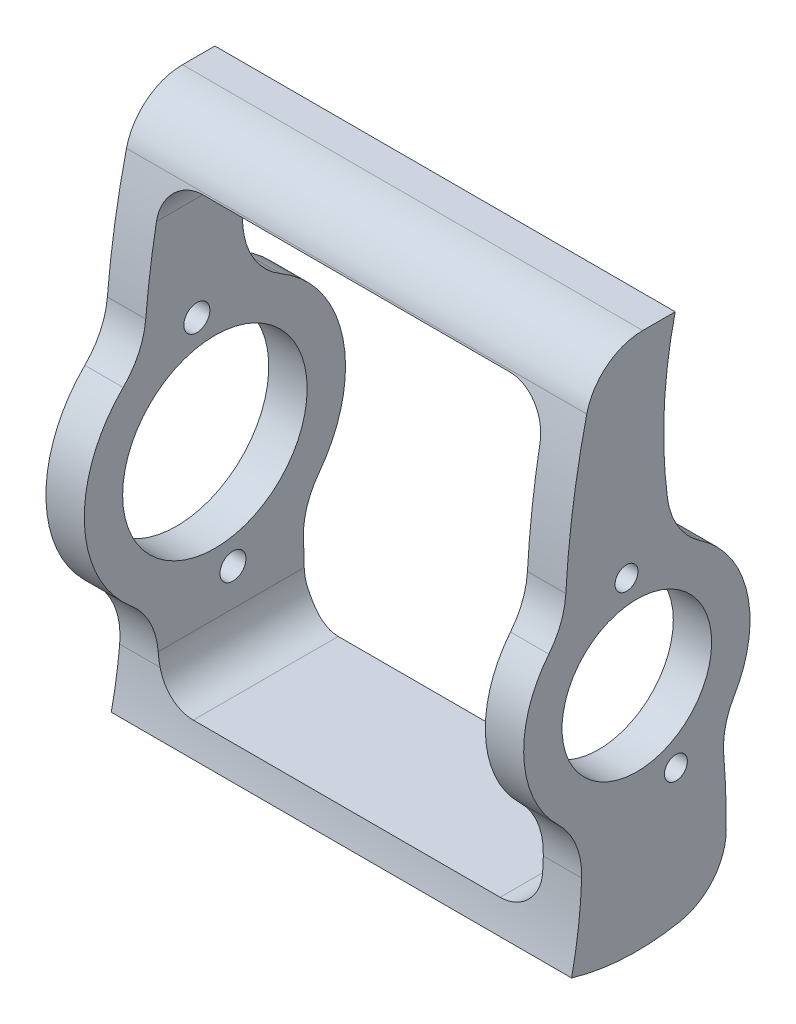
SolidWorks part; units mm, degrees
other "Markup2"
sketch "Sketch9" plane through (31.75, 50.4016, 20.35) normal (0.8402, 0.4575, 0.2911) x (0.3274, 0, -0.9449)
material "AISI 4340 Steel, normalized"
ref_plane "Front Plane" through (0, 0, 0) normal (0, 0, 1) x (1, 0, 0)
ref_plane "Top Plane" through (0, 0, 0) normal (0, 1, 0) x (1, 0, 0)
ref_plane "Right Plane" through (0, 0, 0) normal (1, 0, 0) x (0, 0, -1)
other "Center of Mass"
sketch "Weapon Layout" plane through (0, 0, 0) normal (1, 0, 0) x (0, 0, -1)
  line L0 (-6.35, 50.4016) -> (6.35, 50.4016) construction
  line L1 (-10.8026, -36.5365) -> (14.5626, -35.2071) construction
  line L2 (6.35, 50.4016) -> (-5.4537, 0) construction
  line L3 (6.35, 50.4016) -> (0, 0) construction
  line L4 (0, 0) -> (0, -35.9703) construction
  circle A0 centre (0, 0) radius 14 construction
  circle A1 centre (0, 0) radius 50.8 construction
  circle A2 centre (0, 0) radius 17.175 construction
  circle A3 centre (0, 0) radius 20.35 construction
  arc A4 (-6.35, 50.4016) -> (-20.35, 0) centre (77.3756, 0) ccw construction
  arc A5 (25.0504, -28.707) -> (-25.4024, -28.3959) centre (0, 0) cw construction
  arc A6 (6.35, 50.4016) -> (15.4347, 13.2625) centre (47.4536, 40.7754) ccw construction
  dimension "D1" = 28
  dimension "D2" = 101.6
  dimension "D3" = 3.175
  dimension "D4" = 6.35
  dimension "D5" = 12.7
  dimension "D7" = 6
  dimension "D6" = 12.7
  dimension "D8" = 25.4
  dimension "D9" = 87
sketch "Sketch2" plane through (0, 0, 0) normal (1, 0, 0) x (0, 0, -1)
  line L0 (-6.35, 50.4016) -> (6.35, 50.4016)
  line L1 (-11.3119, -1.6391) -> (0, 0) construction
  line L2 (6.35, 50.4016) -> (-5.4537, 0) construction
  line L3 (-11.6027, 1.0256) -> (-15.24, 50.4016) construction
  arc A0 (-10.8026, -36.5365) -> (14.5626, -35.2071) centre (0, 0) ccw
  arc A1 (-25.4024, -28.3959) -> (25.0504, -28.707) centre (0, 0) ccw construction
  arc A2 (-10.8344, -4.2769) -> (-11.6027, 1.0256) centre (26.3943, 3.8247) cw
  arc A3 (9.8248, 6.4214) -> (11.7322, 0.3423) centre (-25.4469, -7.9841) cw
  arc A4 (-11.6027, 1.0256) -> (-6.35, 50.4016) centre (127.0686, 11.2409) cw
  arc A5 (-10.8344, -4.2769) -> (-10.8026, -36.5365) centre (-85.2917, -20.4799) cw
  arc A6 (6.35, 50.4016) -> (9.8248, 6.4214) centre (76.9988, 33.8561) ccw
  arc A7 (11.7322, 0.3423) -> (14.5626, -35.2071) centre (-112.198, -27.4122) cw
  circle A9 centre (0, 0) radius 11.43 construction
  point P25 (10.9058, 3.4217)
  dimension "D1" = 127
  dimension "D2" = 38.1
  dimension "D3" = 76.2
  dimension "D4" = 38.1
  dimension "D5" = 22.86
  dimension "D6" = 8.89
extrude "Boss-Extrude2" add sketch "Sketch2" along normal mid plane 76.2
sketch "Sketch3" plane through (0, 0, 0) normal (0, 0, 1) x (1, 0, 0)
  line L0 (38.1, 50.4016) -> (-38.1, 50.4016) construction
  line L1 (-31.75, 42.7816) -> (31.75, 42.7816)
  line L2 (-31.75, 42.7816) -> (-31.75, -31.75)
  line L3 (-31.75, -31.75) -> (31.75, -31.75)
  line L4 (31.75, 42.7816) -> (31.75, -31.75)
  line L6 (-38.1, -38.1) -> (38.1, -38.1) construction
  line L7 (-38.1, 50.4016) -> (-38.1, 1.0256) construction
  dimension "D4" = 6.35
  dimension "D1" = 7.62
  dimension "D3" = 6.35
  dimension "D2" = 6.35
extrude "Cut-Extrude1" cut sketch "Sketch3" against normal through all both and the other way through all
fillet "Fillet1" radius 6.35 4 edges at (-31.75, 42.7816, 1.6822) (31.75, 42.7816, 1.6822) (31.75, -31.75, -2.3991) (-31.75, -31.75, -2.3991)
fillet "Fillet3" radius 9.525 2 edges at (0, -35.2071, -14.5626) (0, 50.4016, 6.35)
sketch "Sketch6" plane through (-38.1, 0, 0) normal (-1, 0, 0) x (0, 0, 1)
  circle A0 centre (0, 0) radius 21.62
  dimension "D1" = 43.24
extrude "Boss-Extrude3" add sketch "Sketch6" against normal up to surface (6.35 mm away) up to face at (-31.75, 3.1892, 0.2294)
sketch "Sketch7" plane through (-38.1, 0, 0) normal (-1, 0, 0) x (0, 0, 1)
  circle A0 centre (0, 0) radius 15.27
  arc A1 (9.0967, -19.6131) -> (11.8087, 18.1102) centre (0, 0) ccw construction
  dimension "D1" = 30.54
extrude "Cut-Extrude3" cut sketch "Sketch7" against normal up to next
sketch "Sketch10" plane through (38.1, 0, 0) normal (1, 0, 0) x (0, 0, -1)
  circle A0 centre (0, 0) radius 18.7325
  dimension "D1" = 37.465
extrude "Boss-Extrude4" add sketch "Sketch10" against normal up to surface (6.35 mm away) up to face at (31.75, 3.1892, 0.2294)
sketch "Sketch5" plane through (38.1, 0, 0) normal (1, 0, 0) x (0, 0, -1)
  circle A0 centre (0, 0) radius 12.3825
  circle A1 centre (0, 0) radius 6.35 construction
  dimension "D1" = 12.7
  dimension "D2" = 24.765
extrude "Cut-Extrude2" cut sketch "Sketch5" against normal up to next
fillet "Fillet2" radius 12.7 8 edges at (-34.925, 18.1102, 11.8087) (-34.925, -19.6131, 9.0967) (-34.925, -16.2092, -14.3069) (-34.925, 20.88, -5.6081) (34.925, 17.6517, -6.271) (34.925, -12.528, -13.9268) (34.925, -16.3145, 9.2057) (34.925, 14.4326, 11.9418)
sketch "Sketch11" plane through (38.1, 0, 0) normal (1, 0, 0) x (0, 0, -1)
  circle A0 centre (-1.7114, 16.2614) radius 1.8986
  circle A1 centre (-1.7114, 16.2614) radius 1.8986 construction
  circle A2 centre (6.465, -15.0189) radius 1.8987
  circle A3 centre (6.465, -15.0189) radius 1.8986 construction
extrude "Cut-Extrude4" cut sketch "Sketch11" against normal up to surface (6.35 mm away) up to face at (31.75, 12.3825, 0)
hole_wizard "#6 Clearance Hole1" positions "Sketch12" profile "Sketch13" hole size "#6" standard "ANSI Inch"
sketch "Sketch12" plane through (-38.1, 0, 0) normal (1, 0, 0) x (0, 0, -1)
  point P0 (-2.9885, 19.3009)
  point P3 (2.9885, -19.3009)
sketch "Sketch13" plane through (-38.1, 19.3009, 2.9885) normal (0, 1, 0) x (0, 0, 1)
  line L0 (0, 0) -> (0, 8.9134)
  line L1 (0, 8.9134) -> (2.1526, 7.62)
  line L2 (2.1526, 7.62) -> (2.1526, 0)
  line L5 (2.1526, 0) -> (0, 0)
  line L10 (0, 8.9134) -> (-2.1527, 7.62) construction
  line L11 (0, -6.35) -> (0, 107.95) construction
  dimension "Hole Dia." = 4.3053
  dimension "Hole Depth" = 7.62
  dimension "Drill Angle" = 118
other "Center of Mass Reference Point1"
equation "\"D1@Weapon Layout\" = 28mm"
equation "\"D1@Sketch6\"=\"bearing OD L\"+1/2in+0.1in"
equation "\"D2@Sketch3\"=\"D3@Sketch3\""
equation "\"D1@Sketch7\"=\"bearing OD L\"+0.1in"
equation "\"D2@Sketch5\"=\"bearing OD R\" + .1"
equation "\"D1@Sketch10\"=\"bearing OD R\" + 1/2 + .1"
equation "\"bearing OD R\"= 7 / 8"
equation "\"bearing OD L\"= 28mm"
